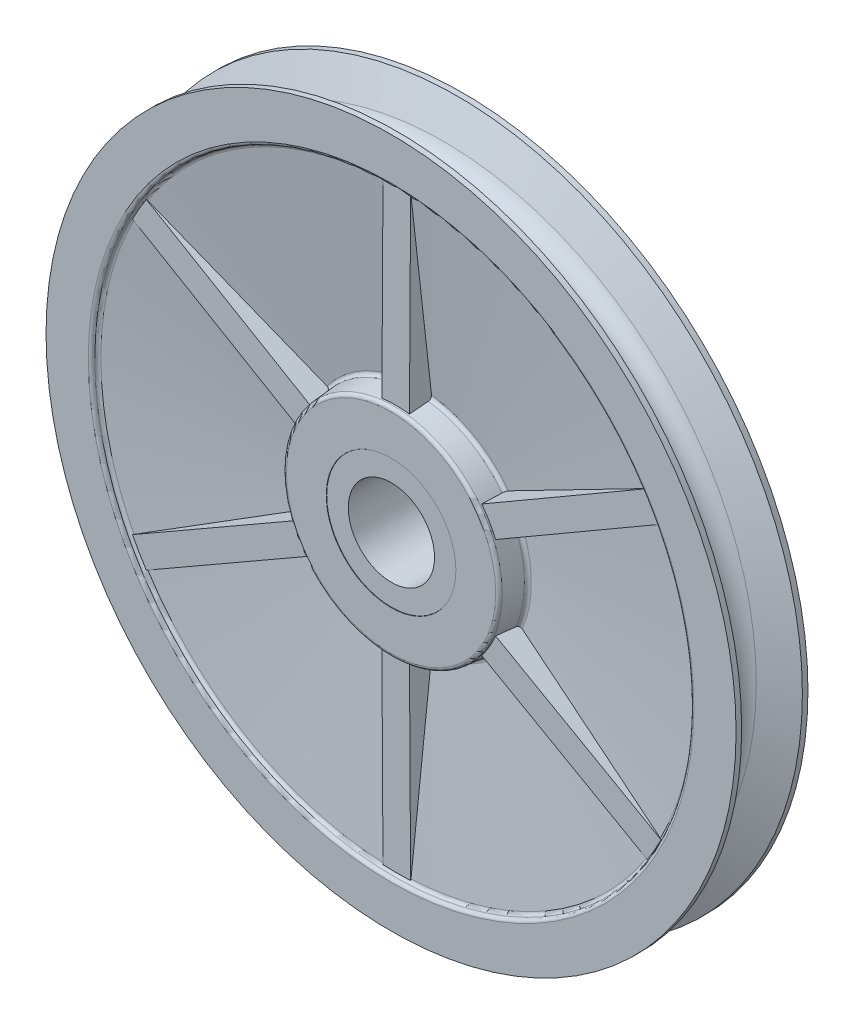
SolidWorks part; units mm, degrees
ref_plane "Front" through (0, 0, 0) normal (0, 0, 1) x (1, 0, 0)
ref_plane "Top" through (0, 0, 0) normal (0, 1, 0) x (1, 0, 0)
ref_plane "Right" through (0, 0, 0) normal (1, 0, 0) x (0, 0, -1)
sketch "Sketch1" plane through (0, 0, 0) normal (1, 0, 0) x (0, 0, -1)
  line L0 (6.7056, 76.2) -> (7.9375, 76.2)
  line L1 (-6.7056, 76.2) -> (-7.9375, 76.2)
  line L2 (-6.7056, 76.2) -> (-3.6467, 69.0776)
  line L3 (7.9375, 23.8125) -> (7.9375, 14.2875)
  line L4 (7.8613, 9.525) -> (-7.8613, 9.525)
  line L5 (-7.9375, 14.2875) -> (-7.9375, 23.8125)
  line L6 (6.7056, 76.2) -> (3.6467, 69.0776)
  line L8 (-7.9375, 0) -> (7.9375, 0) construction
  line L10 (7.9375, 76.2) -> (7.9375, 66.167)
  line L12 (-7.9375, 14.2875) -> (-7.8613, 14.2875)
  line L13 (-7.8613, 14.2875) -> (-7.8613, 9.525)
  line L14 (0, 66.675) -> (0, -66.675) construction
  line L15 (7.8613, 14.2875) -> (7.9375, 14.2875)
  line L16 (7.8613, 14.2875) -> (7.8613, 9.525)
  line L17 (-7.9375, 76.2) -> (-7.9375, -76.2) construction
  line L18 (-7.9375, 66.167) -> (-6.6675, 66.167)
  line L19 (-6.6675, 66.167) -> (-1.905, 23.8125)
  line L20 (-1.905, 23.8125) -> (-7.9375, 23.8125)
  line L21 (-7.9375, 66.167) -> (-7.9375, 76.2)
  line L22 (7.9375, 66.167) -> (6.6675, 66.167)
  line L23 (6.6675, 66.167) -> (1.905, 23.8125)
  line L24 (1.905, 23.8125) -> (7.9375, 23.8125)
  arc A0 (-3.6467, 69.0776) -> (3.6467, 69.0776) centre (0, 70.6437) ccw
  circle A1 centre (0, 70.6437) radius 3.9687 construction
  circle A2 centre (0, 0) radius 9.525 construction
  circle A3 centre (0, 0) radius 14.2875 construction
  circle A4 centre (0, 0) radius 23.8125 construction
  circle A5 centre (0, -70.6437) radius 3.9687 construction
  point P28 (-7.9375, 0)
  dimension "Rope Dia" = 7.9375
  dimension "Shaft Dia" = 19.05
  dimension "D1" = 28.575
  dimension "D3" = 47.625
  dimension "Wd" = 15.875
  dimension "D8" = 1.2319
  dimension "D9" = 0.0762
  dimension "Groove Dia" = 133.35
  dimension "OD" = 152.4
  dimension "D4" = 0.508
  dimension "D2" = 1.27
  dimension "D5" = 3.81
revolve "Revolve1" add sketch "Sketch1" angle 360 about L8
sketch "Sketch2" plane through (0, 0, 0) normal (0, 0, 1) x (1, 0, 0)
  circle A0 centre (0, 0) radius 14.2875 construction
  circle A1 centre (0, 0) radius 14.2875
extrude "Cut-Extrude-Thin1" cut sketch "Sketch2" against normal through all and the other way through all thin thin type one direction wall 0.0254
draft "Draft1" type of draft neutral plane draft angle 5 faces to draft 2 face at (23.8125, 0, 7.9375) face at (66.167, 0, 6.6675) neutral plane through (0, 66.167, 7.9375) neutral plane normal (0, 0, 1) parameters "D1"=5
draft "Draft2" type of draft neutral plane draft angle 15 faces to draft 2 face at (23.8125, 0, -1.905) face at (66.167, 0, -7.9375) neutral plane through (0, 76.2, -7.9375) neutral plane normal (0, 0, -1) parameters "D1"=15
fillet "Fillet1" radius 0.762 4 edges at (66.167, 0, 7.9375) (66.167, 0, -7.9375) (23.8125, 0, 7.9375) (23.8125, 0, -7.9375)
fillet "Fillet2" radius 0.762 2 edges at (-24.3351, 0, 1.9638) (66.0548, 0, 6.6549)
sketch "Sketch5" plane through (0, 0, 0) normal (1, 0, 0) x (0, 0, -1)
  line L0 (-6.9215, 22.5425) -> (-6.6675, 66.167)
  line L1 (0, 66.675) -> (0, -66.675) construction
  line L6 (-6.6675, 66.167) -> (0, 66.167)
  line L7 (0, 66.167) -> (0, 14.2875)
  line L11 (-6.9215, 22.5425) -> (-6.9215, 14.2875)
  line L12 (-6.9215, 14.2875) -> (0, 14.2875)
  line L13 (-1.905, 23.8125) -> (-7.9375, 23.8125) construction
  line L14 (-7.9375, 14.2875) -> (-7.9375, 23.8125) construction
  dimension "D1" = 1.27
  dimension "D2" = 1.016
extrude "Boss-Extrude1" add sketch "Sketch5" along normal mid plane 6.096
mirror "Mirror1" about plane through (0, 0, 0) normal (0, 0, 1) of "Boss-Extrude1"
pattern_circular "CirPattern1" count 6 over 360 about axis through (0, 0, 7.9375) along (0, 0, 1) of "Mirror1", "Boss-Extrude1"
equation "\"D1@Sketch1\" = \"Shaft Dia@Sketch1\" * 1.5"
equation "\"D3@Sketch1\" = \"Shaft Dia@Sketch1\" * 2.5"
equation "\"D1@Boss-Extrude1\" = \"OD@Sketch1\" * .04"
